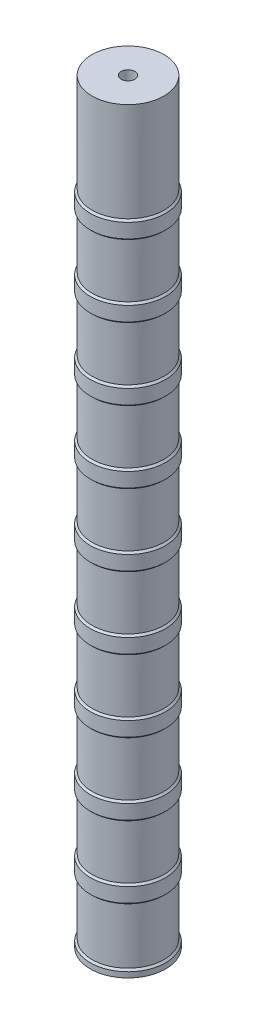
SolidWorks part; units mm, degrees
ref_plane "前视基准面" through (0, 0, 0) normal (0, 0, 1) x (1, 0, 0)
ref_plane "上视基准面" through (0, 0, 0) normal (0, 1, 0) x (1, 0, 0)
ref_plane "右视基准面" through (0, 0, 0) normal (1, 0, 0) x (0, 0, -1)
sketch "草图1" plane through (0, 0, 0) normal (0, 1, 0) x (1, 0, 0)
  circle A0 centre (0, 0) radius 10
  dimension "D1" = 20
extrude "凸台-拉伸1" add sketch "草图1" along normal blind 210
ref_plane "基准面1" through (0, 100, 0) normal (0, -1, 0) x (-1, 0, 0)
sketch "草图2" plane through (0, 100, 0) normal (0, -1, 0) x (-1, 0, 0)
  circle A0 centre (0, 0) radius 10.5
  dimension "D1" = 21
extrude "凸台-拉伸2" add sketch "草图2" along normal mid plane 3
chamfer "倒角1" distance 1 angle 45 2 edges at (0, 101.5, -10) (0, 98.5, -10)
pattern_linear "阵列(线性)1" count 5 spacing 20 along (0, 1, 0) count 5 spacing 20 along (0, -1, 0) of "凸台-拉伸2", "倒角1" pattern seed only yes
sketch "草图3" plane through (0, 210, 0) normal (0, 1, 0) x (1, 0, 0)
  circle A0 centre (0, 0) radius 1.9
  dimension "D1" = 3.8
extrude "切除-拉伸1" cut sketch "草图3" against normal through all both
sketch "草图11" plane through (0, 0, 0) normal (0, -1, 0) x (1, 0, 0)
  circle A0 centre (0, 0) radius 5.2
  dimension "D1" = 10.4
extrude "切除-拉伸2" cut sketch "草图11" against normal blind 10
sketch "草图12" plane through (0, 0, 0) normal (0, -1, 0) x (1, 0, 0)
  circle A0 centre (0, 0) radius 10.5
  circle A1 centre (0, 0) radius 5
  dimension "D1" = 21
  dimension "D2" = 10
extrude "凸台-拉伸3" add sketch "草图12" against normal blind 1.5
chamfer "倒角2" distance 0.5 angle 45 1 edges at (0, 1.5, -10)
